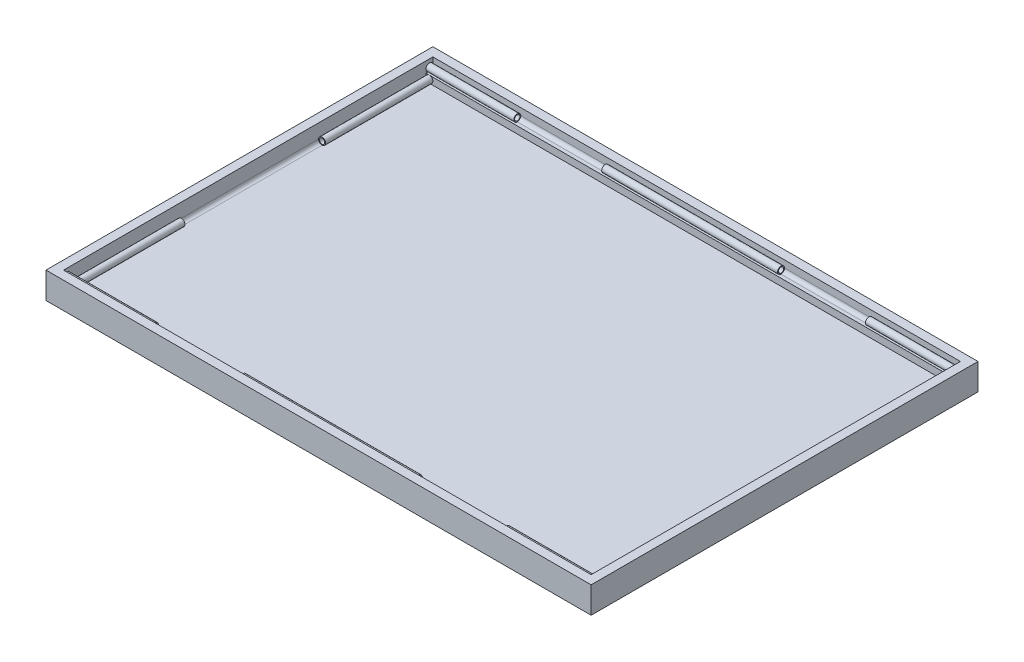
SolidWorks part; units mm, degrees
ref_plane "前视基准面" through (0, 0, 0) normal (0, 0, 1) x (1, 0, 0)
ref_plane "上视基准面" through (0, 0, 0) normal (0, 1, 0) x (1, 0, 0)
ref_plane "右视基准面" through (0, 0, 0) normal (1, 0, 0) x (0, 0, -1)
sketch "草图1" plane through (0, 0, 0) normal (0, 1, 0) x (1, 0, 0)
  line L1 (-154.3396, 132.8302) -> (155.6604, 132.8302)
  line L2 (-154.3396, 132.8302) -> (-154.3396, -87.1698)
  line L3 (-154.3396, -87.1698) -> (155.6604, -87.1698)
  line L4 (155.6604, 132.8302) -> (155.6604, -87.1698)
  dimension "D1" = 310
  dimension "D2" = 220
extrude "凸台-拉伸1" add sketch "草图1" along normal blind 15
sketch "草图2" plane through (0, 15, 0) normal (0, 1, 0) x (1, 0, 0)
  line L0 (-154.3396, 132.8302) -> (-154.3396, -87.1698) construction
  line L1 (-149.3396, 127.8302) -> (150.6604, 127.8302)
  line L2 (-149.3396, 127.8302) -> (-149.3396, -82.1698)
  line L3 (-149.3396, -82.1698) -> (150.6604, -82.1698)
  line L4 (150.6604, 127.8302) -> (150.6604, -82.1698)
  line L5 (155.6604, -87.1698) -> (155.6604, 132.8302) construction
  line L6 (155.6604, 132.8302) -> (-154.3396, 132.8302) construction
  line L7 (-154.3396, -87.1698) -> (155.6604, -87.1698) construction
  dimension "D1" = 5
  dimension "D2" = 5
  dimension "D3" = 5
  dimension "D4" = 5
extrude "切除-拉伸4" cut sketch "草图2" against normal blind 6
ref_plane "基准面2" through (150.6604, 0, 0) normal (1, 0, 0) x (0, 0, -1)
sketch "草图6" plane through (0, 9, 0) normal (0, 1, 0) x (1, 0, 0)
  line L0 (150.6604, -6.6) -> (150.6604, 6.6) construction
  line L1 (-149.3396, 127.8302) -> (150.6604, 127.8302)
  line L2 (-149.3396, 127.8302) -> (-149.3396, 125.8302)
  line L3 (-149.3396, 125.8302) -> (150.6604, 125.8302)
  line L4 (150.6604, 127.8302) -> (150.6604, 125.8302)
  line L6 (-149.3396, -82.1698) -> (150.6604, -82.1698)
  line L7 (-149.3396, -82.1698) -> (-149.3396, -80.1698)
  line L8 (-149.3396, -80.1698) -> (150.6604, -80.1698)
  line L9 (150.6604, -82.1698) -> (150.6604, -80.1698)
  dimension "D1" = 2
  dimension "D2" = 2
extrude "凸台-拉伸3" add sketch "草图6" along normal blind 2
sketch "草图8" plane through (150.6604, 0, 0) normal (1, 0, 0) x (0, 0, -1)
  line L0 (-87.1698, 15) -> (-87.1698, 0) construction
  line L1 (-87.1698, 15) -> (132.8302, 15) construction
  circle A0 centre (-80.1698, 11) radius 2
  dimension "D1" = 7
  dimension "D2" = 4
extrude "切除-拉伸5" cut sketch "草图8" against normal blind 300
extrude "拉伸-薄壁1" add sketch "草图8<2>" against normal blind 300 thin thin type one direction reverse wall 0.5
sketch "草图8<2>" plane through (150.6604, 0, 0) normal (1, 0, 0) x (0, 0, -1) same geometry as "草图8"
sketch "草图10" plane through (150.6604, 0, 0) normal (1, 0, 0) x (0, 0, -1)
  line L0 (132.8302, 15) -> (132.8302, 0) construction
  line L1 (-87.1698, 15) -> (132.8302, 15) construction
  circle A0 centre (125.8302, 11) radius 2
  dimension "D1" = 7
  dimension "D2" = 4
extrude "切除-拉伸6" cut sketch "草图10" against normal blind 300
extrude "拉伸-薄壁2" add sketch "草图10<2>" against normal blind 300 thin thin type one direction reverse wall 0.5
sketch "草图10<2>" plane through (150.6604, 0, 0) normal (1, 0, 0) x (0, 0, -1) same geometry as "草图10"
ref_plane "基准面3" through (100.6604, 0, 0) normal (1, 0, 0) x (0, 0, -1)
ref_plane "基准面4" through (-49.3396, 0, 0) normal (1, 0, 0) x (0, 0, -1)
sketch "草图12" plane through (100.6604, 0, 0) normal (1, 0, 0) x (0, 0, -1)
  line L0 (-87.1698, 15) -> (-87.1698, 0) construction
  line L1 (-87.1698, 15) -> (132.8302, 15) construction
  line L2 (132.8302, 15) -> (132.8302, 0) construction
  circle A0 centre (-80.1698, 11) radius 2
  circle A1 centre (125.8302, 11) radius 2
  dimension "D1" = 4
  dimension "D4" = 7
  dimension "D2" = 7
  dimension "D3" = 4
  dimension "D5" = 4
extrude "切除-拉伸7" cut sketch "草图12" against normal blind 50
sketch "草图13" plane through (-49.3396, 0, 0) normal (1, 0, 0) x (0, 0, -1)
  line L0 (-87.1698, 15) -> (-87.1698, 0) construction
  line L1 (-87.1698, 15) -> (132.8302, 15) construction
  line L2 (132.8302, 15) -> (132.8302, 0) construction
  circle A0 centre (-80.1698, 11) radius 2
  circle A1 centre (125.8302, 11) radius 2
  dimension "D1" = 7
  dimension "D3" = 7
  dimension "D2" = 4
  dimension "D4" = 4
extrude "切除-拉伸8" cut sketch "草图13" against normal blind 50
ref_plane "基准面5" through (0, 0, 78.1698) normal (0, 0, 1) x (1, 0, 0)
sketch "草图14" plane through (0, 0, 78.1698) normal (0, 0, 1) x (1, 0, 0)
  line L0 (-154.3396, 15) -> (-154.3396, 0) construction
  line L3 (-154.3396, 15) -> (155.6604, 15) construction
  line L4 (155.6604, 15) -> (155.6604, 0) construction
  circle A0 centre (-147.3396, 7) radius 2
  circle A1 centre (148.6604, 7) radius 2
  dimension "D1" = 7
  dimension "D3" = 7
  dimension "D2" = 8
  dimension "D4" = 8
sketch "草图15" plane through (0, 9, 0) normal (0, 1, 0) x (1, 0, 0)
  line L0 (-8.25, -78.1698) -> (8.25, -78.1698) construction
  line L1 (-149.3396, 123.8302) -> (150.6604, 123.8302)
  line L2 (-149.3396, 123.8302) -> (-149.3396, -78.1698)
  line L3 (-149.3396, -78.1698) -> (150.6604, -78.1698)
  line L4 (150.6604, 123.8302) -> (150.6604, -78.1698)
  line L5 (150.6604, -80.1698) -> (150.6604, 125.8302) construction
extrude "切除-拉伸9" cut sketch "草图15" against normal blind 4
sketch "草图16" plane through (0, 5, 0) normal (0, 1, 0) x (1, 0, 0)
  line L0 (-149.3396, -78.1698) -> (-145.3396, -78.1698) construction
  line L1 (-149.3396, 123.8302) -> (-147.3396, 123.8302)
  line L2 (-149.3396, 123.8302) -> (-149.3396, -78.1698)
  line L3 (-149.3396, -78.1698) -> (-147.3396, -78.1698)
  line L4 (-147.3396, 123.8302) -> (-147.3396, -78.1698)
  line L5 (-8.25, -78.1698) -> (8.25, -78.1698) construction
  line L6 (150.6604, 123.8302) -> (148.6604, 123.8302)
  line L7 (150.6604, 123.8302) -> (150.6604, -78.1698)
  line L8 (150.6604, -78.1698) -> (148.6604, -78.1698)
  line L9 (148.6604, 123.8302) -> (148.6604, -78.1698)
  dimension "D1" = 2
extrude "凸台-拉伸4" add sketch "草图16" along normal blind 2
extrude "切除-拉伸10" cut sketch "草图14" against normal blind 202
extrude "拉伸-薄壁3" add sketch "草图14<2>" against normal blind 202 thin thin type one direction reverse wall 0.5
sketch "草图14<2>" plane through (0, 0, 78.1698) normal (0, 0, 1) x (1, 0, 0) same geometry as "草图14"
ref_plane "基准面6" through (0, 0, 17.1698) normal (0, 0, 1) x (1, 0, 0)
sketch "草图18" plane through (0, 0, 17.1698) normal (0, 0, 1) x (1, 0, 0)
  line L0 (-154.3396, 15) -> (-154.3396, 0) construction
  line L1 (-154.3396, 15) -> (155.6604, 15) construction
  line L2 (155.6604, 15) -> (155.6604, 0) construction
  circle A0 centre (-147.3396, 7) radius 2
  circle A1 centre (148.6604, 7) radius 2
  dimension "D1" = 7
  dimension "D3" = 7
  dimension "D2" = 8
  dimension "D4" = 8
extrude "切除-拉伸11" cut sketch "草图18" against normal blind 80
